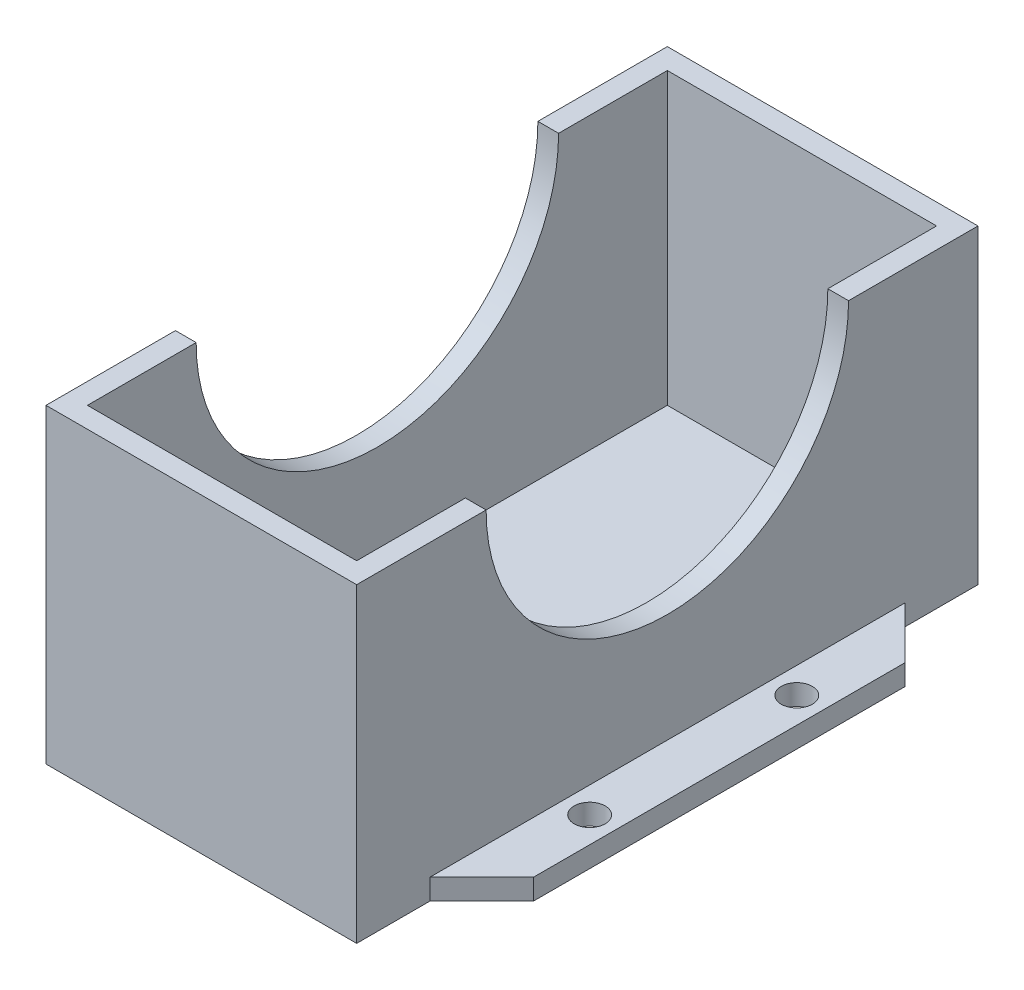
SolidWorks part; units mm, degrees
material "PLA 50%"
ref_plane "Front Plane" through (0, 0, 0) normal (0, 0, 1) x (1, 0, 0)
ref_plane "Top Plane" through (0, 0, 0) normal (0, 1, 0) x (1, 0, 0)
ref_plane "Right Plane" through (0, 0, 0) normal (1, 0, 0) x (0, 0, -1)
ref_axis "X" through (-88.99, 0, 0) along (1, 0, 0)
ref_axis "Y" through (0, 55, 0) along (0, -1, 0)
ref_axis "Z" through (0, 0, -88.99) along (0, 0, 1)
sketch "Sketch1" plane through (0, 0, 0) normal (0, 1, 0) x (1, 0, 0)
  line L0 (0, -30) -> (0, 30)
  line L5 (0, 30) -> (-15, 30)
  line L6 (-15, 30) -> (-15, 22.9289)
  line L7 (-15, 22.9289) -> (-20, 17.9289)
  line L8 (-20, 17.9289) -> (-20, -17.9289)
  line L10 (-15, -22.9289) -> (-15, -30)
  line L11 (-15, -30) -> (0, -30)
  line L12 (-15, -22.9289) -> (-20, -17.9289)
  line L17 (-17.5, -10) -> (-17.5, 10) construction
  line L18 (-15, 0) -> (-20, 0) construction
  circle A0 centre (-17.5, 10) radius 1.5
  circle A1 centre (-17.5, -10) radius 1.5
  point P3 (0, 0)
  point P13 (0, 0)
  point P17 (-17.5, 0)
  point P20 (-17.5, 0)
  dimension "D5" = 3
  dimension "D1" = 135
  dimension "D2" = 15
  dimension "D3" = 5
  dimension "D4" = 60
  dimension "D6" = 20
extrude "Boss-Extrude1" add sketch "Sketch1" along normal blind 2
mirror "Mirror1" about plane through (0, 0, 0) normal (1, 0, 0) of "Boss-Extrude1"
sketch "Sketch2" plane through (0, 2, 0) normal (0, 1, 0) x (1, 0, 0)
  line L0 (-13, 28) -> (-13, -28)
  line L1 (-15, 30) -> (15, 30)
  line L2 (-15, 30) -> (-15, -30)
  line L3 (-15, -30) -> (15, -30)
  line L4 (15, 30) -> (15, -30)
  line L5 (-13, -28) -> (13, -28)
  line L6 (13, 28) -> (13, -28)
  line L7 (-13, 28) -> (13, 28)
  dimension "D1" = 2
extrude "Boss-Extrude2" add sketch "Sketch2" along normal blind 28
sketch "Sketch3" plane through (15, 0, 0) normal (1, 0, 0) x (0, 0, -1)
  line L0 (-30, 30) -> (30, 30) construction
  circle A0 centre (0, 30) radius 17.5
  dimension "D1" = 35
extrude "Cut-Extrude1" cut sketch "Sketch3" against normal through all
